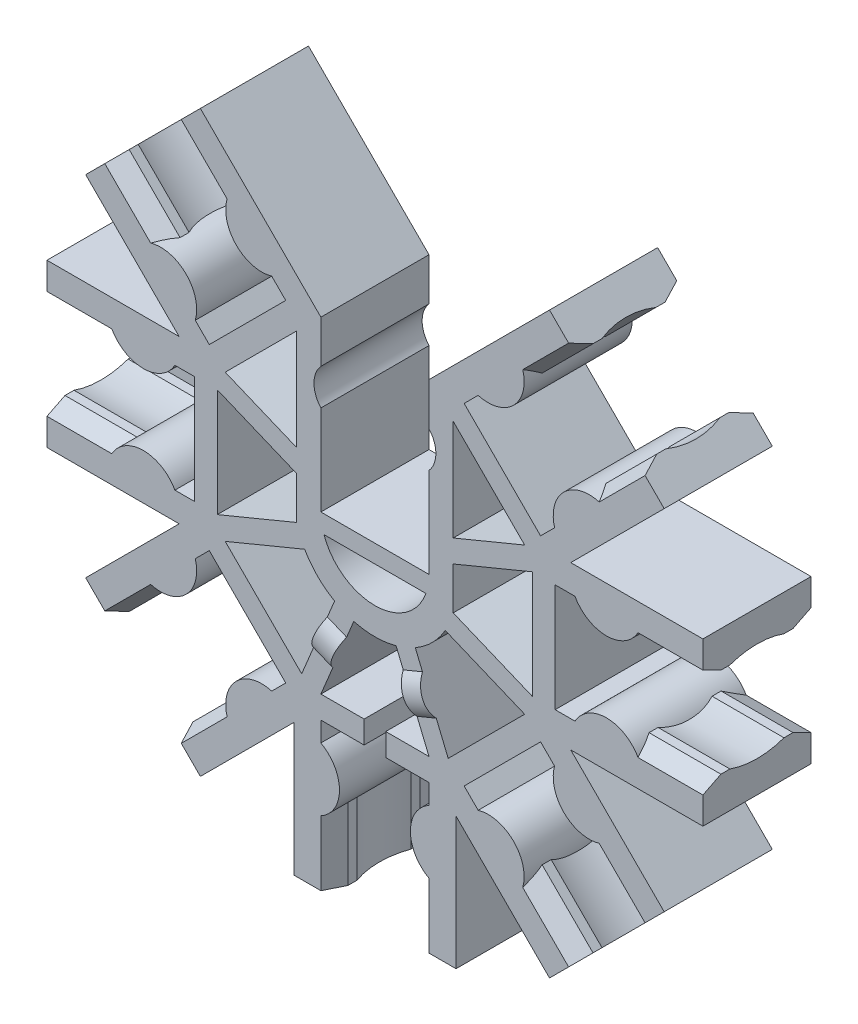
SolidWorks part; units mm, degrees
ref_plane "前视基准面" through (0, 0, 0) normal (0, 0, 1) x (1, 0, 0)
ref_plane "上视基准面" through (0, 0, 0) normal (0, 1, 0) x (1, 0, 0)
ref_plane "右视基准面" through (0, 0, 0) normal (1, 0, 0) x (0, 0, -1)
sketch "草图1" plane through (0, 0, 0) normal (0, 0, 1) x (1, 0, 0)
  line L0 (-4.5, 0) -> (-4.5, -18.2)
  line L1 (4.5, 0) -> (4.5, -18.2)
  line L2 (-4.5, -18.2) -> (-3, -18.2)
  line L3 (-3, -18.2) -> (-3, -14.6)
  line L4 (4.5, -18.2) -> (3, -18.2)
  line L5 (3, -18.2) -> (3, -14.6)
  line L6 (-3, -11.1) -> (-3, -10)
  line L7 (-3, -10) -> (3, -10)
  line L8 (3, -10) -> (3, -11.1)
  arc A0 (4.5, 0) -> (-4.5, 0) centre (0, 0) ccw
  arc A1 (-3, -11.1) -> (-3, -14.6) centre (-3.9682, -12.85) cw
  arc A2 (3, -11.1) -> (3, -14.6) centre (3.9682, -12.85) ccw
  point P1 (0, 4.5)
  dimension "D1" = 9
  dimension "D10" = 14.5
  dimension "D11" = 2
  dimension "D12" = 2
  dimension "D2" = 18.2
  dimension "D3" = 18.2
  dimension "D4" = 1.5
  dimension "D5" = 1.5
  dimension "D6" = 1.1
  dimension "D7" = 1.1
  dimension "D8" = 3.5
  dimension "D9" = 3.5
extrude "凸台-拉伸1" add sketch "草图1" along normal blind 6
sketch "草图3" plane through (0, -18.2, 0) normal (0, -1, 0) x (1, 0, 0)
  line L0 (-3, 6) -> (-3, 0)
  line L1 (-3, 0) -> (-2.5, 1)
  line L2 (-2.5, 1) -> (-2.5, 1.5)
  line L3 (-3, 6) -> (-2.5, 5)
  line L4 (-2.5, 5) -> (-2.5, 4.5)
  line L5 (0, 0) -> (0, 6.4845) construction
  line L6 (3, 0) -> (2.5, 1)
  line L7 (2.5, 1) -> (2.5, 1.5)
  line L8 (2.5, 5) -> (2.5, 4.5)
  line L9 (3, 6) -> (2.5, 5)
  line L10 (3, 6) -> (3, 0)
  arc A0 (-2.5, 1.5) -> (-2.5, 4.5) centre (1.7426, 3) cw
  arc A1 (2.5, 1.5) -> (2.5, 4.5) centre (-1.7426, 3) ccw
  dimension "D7" = 4.5
  dimension "D1" = 0.5
  dimension "D2" = 0.5
  dimension "D3" = 0.5
  dimension "D4" = 0.5
  dimension "D5" = 1.5
  dimension "D6" = 1.5
extrude "凸台-拉伸2" add sketch "草图3" against normal up to next
ref_axis "Axis" through (0, 0, 0) along (0, 0, 1)
pattern_circular "阵列(圆周)1" count 8 over 360 about axis through (0, 0, 0) along (0, 0, 1) of "凸台-拉伸1", "凸台-拉伸2"
sketch "草图4" plane through (0, 0, 0) normal (0, 0, -1) x (-1, 0, 0)
  line L0 (0, 0) -> (-4.5, -10.864) construction
  line L1 (0, 0) -> (4.5, -10.864) construction
  line L2 (0, 0) -> (0, -10) construction
  line L3 (3, -10) -> (-3, -10) construction
  line L4 (-3, -8.75) -> (-0.6, -8.75)
  line L5 (-3, -8.75) -> (-1.1749, -4.3439)
  line L6 (3, -8.75) -> (1.1749, -4.3439)
  line L7 (-8.3085, -4.0659) -> (-3.9024, -2.2408)
  line L8 (-8.3085, -4.0659) -> (-4.0659, -8.3085)
  line L9 (-4.0659, -8.3085) -> (-2.2408, -3.9024)
  line L10 (-4.3439, -1.1749) -> (-4.3439, 1.1749)
  line L11 (-8.75, 3) -> (-8.75, -3)
  line L12 (-8.75, -3) -> (-4.3439, -1.1749)
  line L13 (4.3439, -1.1749) -> (4.3439, 1.1749)
  line L14 (-4.3439, 8.0305) -> (-8.3085, 4.0659)
  line L15 (0, 0) -> (-10.864, 4.5) construction
  line L16 (4.0659, -8.3085) -> (2.2408, -3.9024)
  line L17 (4.0659, -8.3085) -> (8.3085, -4.0659)
  line L18 (8.3085, -4.0659) -> (3.9024, -2.2408)
  line L19 (8.75, -3) -> (4.3439, -1.1749)
  line L20 (8.75, -3) -> (8.75, 3)
  line L21 (0, 0) -> (10.864, 4.5) construction
  line L22 (-8.75, 3) -> (-4.3439, 1.1749)
  line L23 (8.3085, 4.0659) -> (4.3439, 8.0305)
  line L24 (-8.3085, 4.0659) -> (-4.3439, 2.4237)
  line L25 (-4.0659, 8.3085) -> (-2.2408, 3.9024) [skipped]
  line L26 (4.0659, 8.3085) -> (2.2408, 3.9024) [skipped]
  line L27 (-8.3085, 4.0659) -> (-3.9024, 2.2408) [skipped]
  line L28 (8.3085, 4.0659) -> (3.9024, 2.2408) [skipped]
  line L29 (-8.75, 3) -> (-4.3439, 1.1749) [skipped]
  line L30 (8.75, 3) -> (4.3439, 1.1749) [skipped]
  line L31 (8.3085, 4.0659) -> (4.3439, 2.4237)
  line L32 (8.75, 3) -> (4.3439, 1.1749)
  line L33 (-4.3439, 2.4237) -> (-4.3439, 8.0305)
  line L34 (4.3439, 2.4237) -> (4.3439, 8.0305)
  line L35 (-4.5, 10.864) -> (-3, 9.364)
  line L36 (-3, 9.364) -> (-3, 7)
  line L37 (4.5, 10.864) -> (3, 9.364)
  line L38 (3, 9.364) -> (3, 7)
  line L39 (-9.6874, 16.0513) -> (-4.5, 10.864) construction
  line L40 (4.5, 10.864) -> (9.6874, 16.0513) construction
  line L41 (-4.5, 10.864) -> (-4.5, 18.2)
  line L42 (-4.5, 18.2) -> (4.5, 18.2)
  line L43 (4.5, 18.2) -> (4.5, 10.864)
  line L44 (-3, 0) -> (0, 0)
  line L45 (0, 0) -> (3, 0)
  line L46 (-2.8284, -1) -> (2.8284, -1)
  line L47 (-3, 5) -> (-3, 0)
  line L48 (3, 5) -> (3, 0)
  line L49 (-0.6, -8.75) -> (-0.6, -10)
  line L50 (-0.6, -10) -> (0.6, -10)
  line L51 (0.6, -10) -> (0.6, -8.75)
  line L52 (0.6, -8.75) -> (3, -8.75)
  arc A0 (-2.8284, -1) -> (2.8284, -1) centre (0, 0) ccw
  arc A1 (-3.9024, -2.2408) -> (-2.2408, -3.9024) centre (0, 0) ccw
  arc A2 (-1.1749, -4.3439) -> (1.1749, -4.3439) centre (0, 0) ccw
  arc A3 (2.2408, -3.9024) -> (3.9024, -2.2408) centre (0, 0) ccw
  arc A4 (-3, 7) -> (-3, 5) centre (-1.882, 6) ccw
  arc A5 (3, 7) -> (3, 5) centre (1.882, 6) cw
  point P31 (0, 0)
  point P44 (0, 0)
  point P47 (0, 0)
  dimension "D3" = 6
  dimension "D4" = 9
  dimension "D7" = 1.5
  dimension "D1" = 6
  dimension "D2" = 1.25
  dimension "D6" = 1
  dimension "D8" = 2
  dimension "D9" = 5
  dimension "D10" = 1.2
  dimension "D11" = 0.6
  dimension "D5" = 4
extrude "切除-拉伸2" cut sketch "草图4" against normal through all
sketch "草图5" plane through (-0.5329, -0.2207, 0) normal (-0.9239, -0.3827, 0) x (0, 0, 1)
  line L0 (0, -4.4629) -> (0, -9.232) construction
  line L1 (0, -7.5) -> (0, -5.5)
  line L2 (3, -5.5) -> (3, -8.1688) construction
  line L3 (6, -7.5) -> (6, -5.5)
  arc A0 (0, -5.5) -> (0, -7.5) centre (1.118, -6.5) ccw
  arc A1 (6, -5.5) -> (6, -7.5) centre (4.882, -6.5) cw
  dimension "D3" = 1.5
  dimension "D1" = 2
  dimension "D2" = 5.5
  dimension "D4" = 3
extrude "凸台-拉伸3" add sketch "草图5" against normal up to surface (1.1537 mm away) up to face at (3.1533, -6.1055, 3)
sketch "草图6" plane through (0.5329, -0.2207, 0) normal (0.9239, -0.3827, 0) x (0, 0, -1)
  line L0 (0, -9.232) -> (0, -4.4629) construction
  line L1 (-3, -5.5) -> (-3, -7.8679) construction
  line L2 (0, -7.5) -> (0, -5.5)
  line L3 (-6, -7.5) -> (-6, -5.5)
  arc A0 (0, -5.5) -> (0, -7.5) centre (-1.118, -6.5) cw
  arc A1 (-6, -5.5) -> (-6, -7.5) centre (-4.882, -6.5) ccw
  dimension "D1" = 1.5
  dimension "D2" = 5.5
  dimension "D3" = 2
  dimension "D4" = 3
extrude "凸台-拉伸4" add sketch "草图6" against normal up to surface (1.1537 mm away) up to face at (-3.1533, -6.1055, 3)
